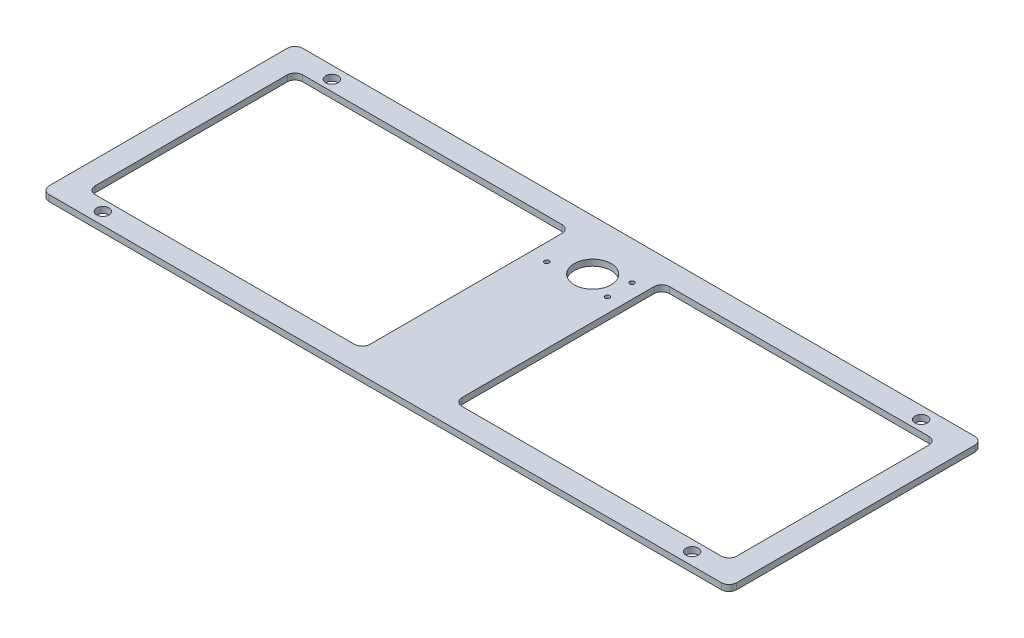
SolidWorks part; units mm, degrees
note: The reader was unsure of these and kept them because the rebuilt part matched: thickness of "Base-Flange1", "Sheet-Metal1", "Sheet-Metal2", "Sheet-Metal3", "Sheet-Metal5", "Sheet-Metal6", "Sheet-Metal7", "Sheet-Metal9", "Sheet-Metal10".
material "6061-T6 (SS)"
ref_plane "Front Plane" through (0, 0, 0) normal (0, 0, 1) x (1, 0, 0)
ref_plane "Top Plane" through (0, 0, 0) normal (0, 1, 0) x (1, 0, 0)
ref_plane "Right Plane" through (0, 0, 0) normal (1, 0, 0) x (0, 0, -1)
sketch "Sketch1" plane through (0, 0, 0) normal (0, 1, 0) x (1, 0, 0)
  line L1 (-60.9596, 49.4555) -> (139.0404, 49.4555)
  line L2 (-60.9596, 49.4555) -> (-60.9596, -33.1445)
  line L3 (-60.9596, -33.1445) -> (139.0404, -33.1445)
  line L4 (139.0404, 49.4555) -> (139.0404, -33.1445)
  dimension "D1" = 82.6
  dimension "D2" = 200
base flange "Base-Flange1" sketch "Sketch1" thickness 2 reverse thickness direction no parameters "D1"=1
sketch "Sketch6" plane through (0, 0, 0) normal (0, 1, 0) x (1, 0, 0)
  line L0 (139.0404, 49.4555) -> (-60.9596, 49.4555) construction
  line L1 (-60.9596, 49.4555) -> (-60.9596, -33.1445) construction
  line L2 (139.0404, -33.1445) -> (139.0404, 49.4555) construction
  line L3 (-60.9596, -33.1445) -> (139.0404, -33.1445) construction
  circle A0 centre (-56.9596, 45.4555) radius 2
  circle A1 centre (-56.9596, -29.1445) radius 2
  circle A2 centre (135.0404, -29.1445) radius 2
  circle A3 centre (135.0404, 45.4555) radius 2
  dimension "D1" = 4
  dimension "D2" = 4
  dimension "D3" = 4
  dimension "D4" = 4
  dimension "D5" = 4
extrude "Cut-Extrude1" cut sketch "Sketch6" against normal through all normal cut yes
sketch "Sketch7" plane through (0, 0, 0) normal (0, 1, 0) x (1, 0, 0)
  line L0 (39.0404, 49.4555) -> (39.0404, -33.1445) construction
  line L6 (139.0404, 49.4555) -> (-60.9596, 49.4555) construction
  line L7 (-60.9596, -33.1445) -> (139.0404, -33.1445) construction
  line L8 (24.0404, 8.1555) -> (54.0404, 8.1555) construction
  line L9 (-53.4596, 41.9555) -> (24.0404, 41.9555)
  line L10 (-53.4596, 41.9555) -> (-53.4596, -25.6445)
  line L11 (-53.4596, -25.6445) -> (24.0404, -25.6445)
  line L12 (24.0404, 41.9555) -> (24.0404, -25.6445)
  line L13 (54.0404, 41.9555) -> (131.5404, 41.9555)
  line L14 (54.0404, 41.9555) -> (54.0404, -25.6445)
  line L15 (54.0404, -25.6445) -> (131.5404, -25.6445)
  line L16 (131.5404, 41.9555) -> (131.5404, -25.6445)
  line L17 (-60.9596, 49.4555) -> (-60.9596, -33.1445) construction
  line L18 (139.0404, -33.1445) -> (139.0404, 49.4555) construction
  point P17 (39.0404, 8.1555)
  point P18 (24.0404, 8.1555)
  dimension "D3" = 7.5
  dimension "D1" = 30
  dimension "D2" = 7.5
  dimension "D4" = 7.5
extrude "Cut-Extrude2" cut sketch "Sketch7" against normal through all normal cut yes
sketch "Sketch8" plane through (-60.9596, 0, 0) normal (-1, 0, 0) x (0, 0, 1)
  line L1 (-49.4555, -2) -> (33.1445, -2)
  line L2 (-49.4555, -2) -> (-49.4555, 0)
  line L3 (-49.4555, 0) -> (33.1445, 0)
  line L4 (33.1445, -2) -> (33.1445, 0)
extrude "Boss-Extrude1" add sketch "Sketch8" along normal blind 12
sketch "Sketch9" plane through (139.0404, 0, 0) normal (1, 0, 0) x (0, 0, -1)
  line L1 (49.4555, 0) -> (-33.1445, 0)
  line L2 (49.4555, 0) -> (49.4555, -2)
  line L3 (49.4555, -2) -> (-33.1445, -2)
  line L4 (-33.1445, 0) -> (-33.1445, -2)
extrude "Boss-Extrude2" add sketch "Sketch9" along normal blind 12
sketch "Sketch10" plane through (0, 0, 0) normal (0, 1, 0) x (1, 0, 0)
  line L0 (-72.9596, -33.1445) -> (-72.9596, 49.4555) construction
  line L1 (-53.4596, -25.6445) -> (-65.4596, -25.6445)
  line L2 (-53.4596, -25.6445) -> (-53.4596, 41.9555)
  line L3 (-53.4596, 41.9555) -> (-65.4596, 41.9555)
  line L4 (-65.4596, -25.6445) -> (-65.4596, 41.9555)
  line L5 (131.5404, -25.6445) -> (143.5404, -25.6445)
  line L6 (131.5404, -25.6445) -> (131.5404, 41.9555)
  line L7 (131.5404, 41.9555) -> (143.5404, 41.9555)
  line L8 (143.5404, -25.6445) -> (143.5404, 41.9555)
  line L9 (151.0404, 49.4555) -> (151.0404, -33.1445) construction
  dimension "D1" = 7.5
  dimension "D2" = 7.5
  dimension "D3" = 67.6
  dimension "D4" = 67.6
extrude "Cut-Extrude3" cut sketch "Sketch10" against normal through all normal cut yes
fillet "Fillet1" radius 2.5 12 edges at (151.0404, -1, -49.4555) (143.5404, -1, -41.9555) (151.0404, -1, 33.1445) (143.5404, -1, 25.6445) (54.0404, -1, 25.6445) (24.0404, -1, 25.6445) (-65.4596, -1, 25.6445) (-72.9596, -1, 33.1445) (54.0404, -1, -41.9555) (24.0404, -1, -41.9555) (-72.9596, -1, -49.4555) (-65.4596, -1, -41.9555)
sketch "Sketch11" plane through (0, 0, 0) normal (0, 1, 0) x (1, 0, 0)
  circle A0 centre (40.5405, 32.9555) radius 6
  point P3 (0, 0)
  dimension "D1" = 12
extrude "Cut-Extrude4" cut sketch "Sketch11" against normal through all normal cut yes
hole_wizard "Ø1.5mm Dowel Hole1" positions "Sketch12" profile "Sketch13" hole size "Ø1.5" standard "ANSI Metric" end condition through all
sketch "Sketch12" plane through (0, 0, 0) normal (0, 1, 0) x (1, 0, 0)
  point P0 (49.3405, 36.9555)
  point P3 (49.3405, 28.9555)
  point P6 (29.5405, 28.9555)
  point P11 (0, 0)
  point P12 (0, 0)
  point P13 (0, 0)
  point P14 (0, 0)
sketch "Sketch13" plane through (49.3405, 0, -36.9555) normal (1, 0, 0) x (0, 0, 1)
  line L0 (0, 0) -> (0, 2)
  line L1 (0, 2) -> (0.75, 2)
  line L2 (0.75, 2) -> (0.75, 0)
  line L5 (0.75, 0) -> (0, 0)
  line L11 (0, -6.35) -> (0, 107.95) construction
  dimension "Thru Hole Dia." = 1.5
  dimension "Thru Hole Depth" = 2
sketch "Bend-Lines1" [suppressed] plane through (0, 0, 0) normal (0, 1, 0) x (1, 0, 0)
sketch "Bounding-Box1" [suppressed] plane through (0, 0, 0) normal (0, 1, 0) x (1, 0, 0)
sheet metal parameters "Sheet-Metal1" thickness 2 parameters "D1"=1
flat pattern "Flat-Pattern1" [suppressed]
sketch "Bend-Lines2" plane through (0, 0, 0) normal (0, 1, 0) x (1, 0, 0)
sketch3d "Bounding-Box2" [suppressed]
  line L0 (-162.0404, -38.5445, 0) -> (60.9596, -38.5445, 0) construction
  line L1 (-162.0404, 49.4555, 0) -> (60.9596, 49.4555, 0) construction
  line L2 (-162.0404, -38.5445, 0) -> (-162.0404, 49.4555, 0) construction
  line L3 (60.9596, -38.5445, 0) -> (60.9596, 49.4555, 0) construction
sheet metal parameters "Sheet-Metal2" thickness 2 parameters "D1"=1
flat pattern "Flat-Pattern1"
sketch "Bend-Lines2" plane through (0, 0, 0) normal (0, 1, 0) x (1, 0, 0)
sketch3d "Bounding-Box2" [suppressed]
  line L0 (-60.9596, -31.5444, 0) -> (162.0404, -31.5445, 0) construction
  line L1 (-60.9595, 49.4555, 0) -> (162.0405, 49.4554, 0) construction
  line L2 (-60.9596, -31.5444, 0) -> (-60.9595, 49.4555, 0) construction
  line L3 (162.0404, -31.5445, 0) -> (162.0405, 49.4554, 0) construction
sheet metal parameters "Sheet-Metal3" thickness 2 parameters "D1"=1
flat pattern "Flat-Pattern1"
sketch "Bend-Lines2" plane through (0, 0, 0) normal (0, 1, 0) x (1, 0, 0)
sketch3d "Bounding-Box2" [suppressed]
  line L0 (139.0404, -33.1445, 0) -> (-60.9596, -33.1445, 0) construction
  line L1 (139.0404, 49.4555, 0) -> (-60.9596, 49.4555, 0) construction
  line L2 (139.0404, -33.1445, 0) -> (139.0404, 49.4555, 0) construction
  line L3 (-60.9596, -33.1445, 0) -> (-60.9596, 49.4555, 0) construction
sheet metal parameters "Sheet-Metal5" thickness 2 parameters "D1"=1
flat pattern "Flat-Pattern1"
sketch "Bend-Lines2" plane through (0, 0, 0) normal (0, 1, 0) x (1, 0, 0)
sketch3d "Bounding-Box2" [suppressed]
  line L0 (139.0404, -33.1445, 0) -> (-72.9596, -33.1445, 0) construction
  line L1 (139.0404, 49.4555, 0) -> (-72.9596, 49.4555, 0) construction
  line L2 (139.0404, -33.1445, 0) -> (139.0404, 49.4555, 0) construction
  line L3 (-72.9596, -33.1445, 0) -> (-72.9596, 49.4555, 0) construction
sheet metal parameters "Sheet-Metal6" thickness 2 parameters "D1"=1
flat pattern "Flat-Pattern1"
sketch "Bend-Lines2" plane through (0, 0, 0) normal (0, 1, 0) x (1, 0, 0)
sketch3d "Bounding-Box2" [suppressed]
  line L0 (151.0404, -33.1445, 0) -> (-72.9596, -33.1445, 0) construction
  line L1 (151.0404, 49.4555, 0) -> (-72.9596, 49.4555, 0) construction
  line L2 (151.0404, -33.1445, 0) -> (151.0404, 49.4555, 0) construction
  line L3 (-72.9596, -33.1445, 0) -> (-72.9596, 49.4555, 0) construction
sheet metal parameters "Sheet-Metal7" thickness 2 parameters "D1"=1
flat pattern "Flat-Pattern1"
sketch "Bend-Lines2" plane through (0, 0, 0) normal (0, 1, 0) x (1, 0, 0)
sketch3d "Bounding-Box2" [suppressed]
  line L0 (-72.9596, -33.1445, 0) -> (151.0404, -33.1445, 0) construction
  line L1 (-72.9596, 49.4555, 0) -> (151.0404, 49.4555, 0) construction
  line L2 (-72.9596, -33.1445, 0) -> (-72.9596, 49.4555, 0) construction
  line L3 (151.0404, -33.1445, 0) -> (151.0404, 49.4555, 0) construction
sheet metal parameters "Sheet-Metal9" thickness 2 parameters "D1"=1
flat pattern "Flat-Pattern1"
sketch "Bend-Lines2" plane through (0, 0, 0) normal (0, 1, 0) x (1, 0, 0)
sketch3d "Bounding-Box2" [suppressed]
  line L0 (-72.9596, -33.1445, 0) -> (151.0404, -33.1445, 0) construction
  line L1 (-72.9596, 49.4555, 0) -> (151.0404, 49.4555, 0) construction
  line L2 (-72.9596, -33.1445, 0) -> (-72.9596, 49.4555, 0) construction
  line L3 (151.0404, -33.1445, 0) -> (151.0404, 49.4555, 0) construction
sheet metal parameters "Sheet-Metal10" thickness 2 parameters "D1"=1
flat pattern "Flat-Pattern1"
sketch "Bend-Lines2" plane through (0, 0, 0) normal (0, 1, 0) x (1, 0, 0)
sketch3d "Bounding-Box2" [suppressed]
  line L0 (-72.9596, -33.1445, 0) -> (151.0404, -33.1445, 0) construction
  line L1 (-72.9596, 49.4555, 0) -> (151.0404, 49.4555, 0) construction
  line L2 (-72.9596, -33.1445, 0) -> (-72.9596, 49.4555, 0) construction
  line L3 (151.0404, -33.1445, 0) -> (151.0404, 49.4555, 0) construction
equation "\"2.5.00mm\"=10"
